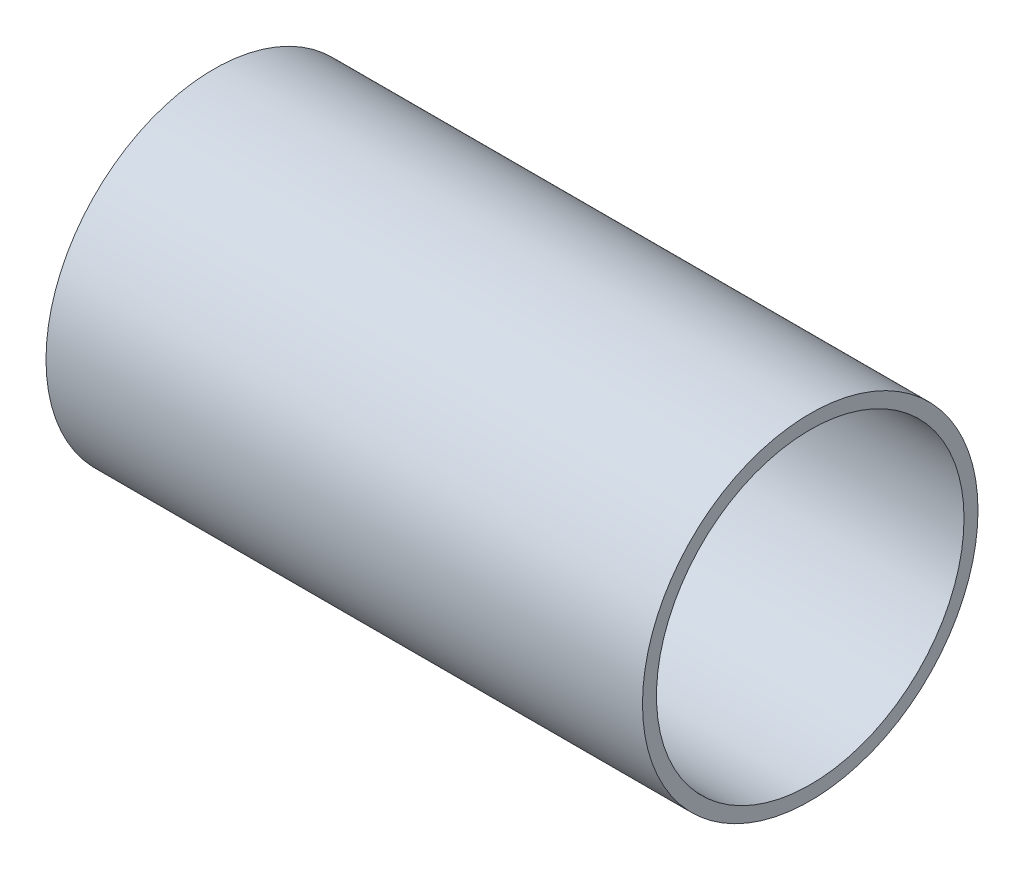
SolidWorks part; units mm, degrees
ref_plane "Plano frontal" through (0, 0, 0) normal (0, 0, 1) x (1, 0, 0)
ref_plane "Plano superior" through (0, 0, 0) normal (0, 1, 0) x (1, 0, 0)
ref_plane "Plano direito" through (0, 0, 0) normal (1, 0, 0) x (0, 0, -1)
sketch "Esboço1" plane through (0, 0, 0) normal (0, 0, 1) x (1, 0, 0)
  line L0 (27, -15) -> (92.6435, -15) construction
  line L1 (-27, -15) -> (27, -15) construction
  line L2 (-27, -15) -> (-27, 15) construction
  line L3 (-27, 15) -> (27, 15) construction
  line L4 (27, -15) -> (27, 15) construction
  line L5 (-27, -15) -> (27, 15) construction
  line L6 (-27, 15) -> (27, -15) construction
  point P0 (0, 0)
  point P6 (37, -15)
  dimension "D1" = 30
  dimension "D2" = 54
  dimension "D3" = 10
ref_plane "Plano1" through (37, 0, 0) normal (1, 0, 0) x (0, 0, -1)
sketch "Esboço2" plane through (37, 0, 0) normal (1, 0, 0) x (0, 0, -1)
  circle A0 centre (0, 0) radius 18
  point P2 (0, -18)
  dimension "D1" = 36
  dimension "D2" = 3
extrude "Ressalto-extrusão1" add sketch "Esboço2" against normal blind 64 contours A0
shell "Casca4" thickness 1.5 removed face at (-27, 0, -18) removed face at (37, 0, -18)
ref_plane "Plano2" through (0, 0, 18) normal (0, 0, 1) x (1, 0, 0)
sketch "Esboço10" plane through (0, 0, 18) normal (0, 0, 1) x (1, 0, 0)
  line L0 (-27, 18) -> (26.6769, 18)
  line L1 (37, 18) -> (-27, 18) construction
  line L2 (-27, 18) -> (-27, 10)
  line L3 (-27, -15) -> (-27, 15) construction
  line L4 (-27, 10) -> (-7.1575, 10)
  line L5 (27, 10) -> (15.043, 10)
  line L6 (27, -15) -> (27, 15) construction
  line L7 (15.043, 10) -> (15.043, 0)
  line L8 (15.043, 0) -> (3.6225, 0)
  line L11 (-27, 15) -> (27, 15) construction
  dimension "D1" = 5
